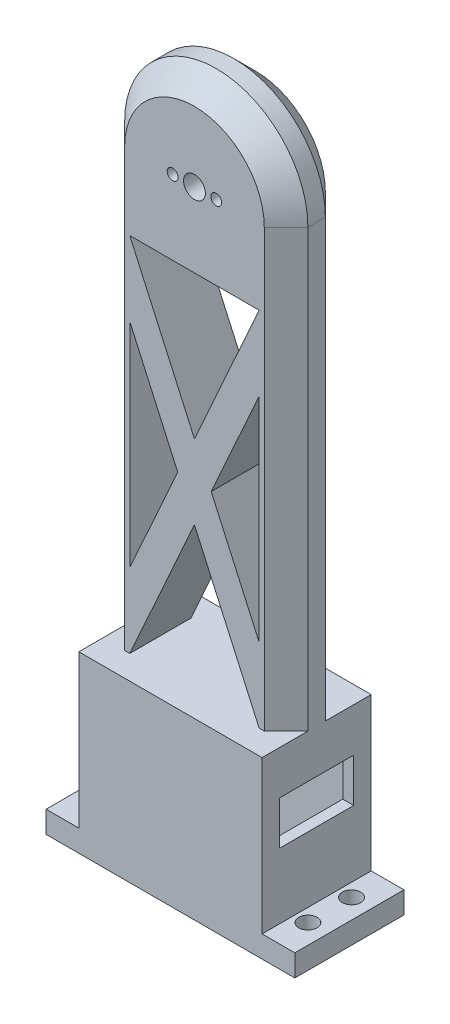
SolidWorks part; units mm, degrees
ref_plane "Front Plane" through (0, 0, 0) normal (0, 0, 1) x (1, 0, 0)
ref_plane "Top Plane" through (0, 0, 0) normal (0, 1, 0) x (1, 0, 0)
ref_plane "Right Plane" through (0, 0, 0) normal (1, 0, 0) x (0, 0, -1)
sketch "Sketch1" plane through (0, 0, 0) normal (0, 0, 1) x (1, 0, 0)
  line L2 (-21, 0) -> (-21, -100)
  line L3 (-21, -100) -> (21, -100)
  line L4 (21, 0) -> (21, -100)
  arc A1 (21, 0) -> (-21, 0) centre (0, 0) ccw
  point P1 (0, 0)
  dimension "D1" = 100
  dimension "D2" = 42
extrude "Boss-Extrude1" add sketch "Sketch1" along normal mid plane 14
sketch "Sketch2" plane through (0, -100, 0) normal (0, -1, 0) x (1, 0, 0)
  line L1 (21, -12.5) -> (-21, -12.5)
  line L2 (21, -12.5) -> (21, 12.5)
  line L3 (21, 12.5) -> (-21, 12.5)
  line L4 (-21, -12.5) -> (-21, 12.5)
  line L5 (21, -12.5) -> (-21, 12.5) construction
  line L6 (21, 12.5) -> (-21, -12.5) construction
  point P0 (0, 0)
  dimension "D1" = 42
  dimension "D2" = 25
extrude "Boss-Extrude2" add sketch "Sketch2" along normal blind 40 separate body
shell "Shell1" thickness 2.5 removed face at (0, -140, 0)
combine bodies "Combine1" operation type add bodies to combine 101 102
sketch "Sketch8" plane through (0, 0, 7) normal (0, 0, 1) x (1, 0, 0)
  line L0 (-10.25, 0) -> (10.25, 0)
  circle A0 centre (0, 0) radius 10.25
  circle A1 centre (-5, 0) radius 1.25
  circle A2 centre (5, 0) radius 1.25
  circle A3 centre (0, 0) radius 2.5
  dimension "D1" = 20.5
  dimension "D2" = 2.5
  dimension "D3" = 2.5
  dimension "D4" = 10
  dimension "D6" = 5
  dimension "D5" = 5.25
extrude "Cut-Extrude5" cut sketch "Sketch8" against normal up to next contours L0 A1 | L0 A1 | L0 A2 | L0 A2 | L0 A3 | L0 A3 | A3 region at (5, -0.5305, 7) region at (5, 0.5305, 7) region at (0, -1.061, 7) region at (0, 1.061, 7) region at (-5, 0.5305, 7) region at (-5, -0.5305, 7)
sketch "Sketch9" plane through (0, -140, 0) normal (0, -1, 0) x (1, 0, 0)
  line L5 (-21, -12.5) -> (21, -12.5) construction
  line L10 (-18.5, 12.5) -> (-28.5, 12.5)
  line L11 (-18.5, 12.5) -> (-18.5, -12.5)
  line L12 (-18.5, -12.5) -> (-28.5, -12.5)
  line L13 (-28.5, 12.5) -> (-28.5, -12.5)
  line L14 (21, 12.5) -> (-21, 12.5) construction
  line L15 (-18.5, 10) -> (-18.5, -10) construction
  line L16 (0, -12.5) -> (0, 12.5)
  line L17 (18.5, -12.5) -> (28.5, -12.5)
  line L18 (28.5, 12.5) -> (28.5, -12.5)
  line L19 (18.5, 12.5) -> (28.5, 12.5)
  line L20 (18.5, 12.5) -> (18.5, -12.5)
  point P18 (0, 0)
  dimension "D1" = 10
extrude "Boss-Extrude3" add sketch "Sketch9" against normal blind 5 contours L10 L13 L12 | L19 L17 L18 region at (-23.5, -140, 0) region at (23.5, -140, 0)
sketch "Sketch10" plane through (21, 0, 0) normal (1, 0, 0) x (0, 0, -1)
  line L0 (-12.5, -135) -> (-12.5, -100) construction
  line L1 (-8.5, -110) -> (8.5, -110)
  line L2 (-8.5, -110) -> (-8.5, -120)
  line L3 (-8.5, -120) -> (8.5, -120)
  line L4 (8.5, -110) -> (8.5, -120)
  line L5 (12.5, -135) -> (12.5, -100) construction
  line L6 (12.5, -100) -> (7, -100) construction
  dimension "D1" = 4
  dimension "D2" = 4
  dimension "D3" = 10
  dimension "D4" = 10
extrude "Cut-Extrude6" cut sketch "Sketch10" against normal up to next
sketch "Sketch12" plane through (0, 0, 7) normal (0, 0, 1) x (1, 0, 0)
  line L0 (21, 0) -> (21, -17.058)
  line L2 (14.8239, -34.116) -> (3.838, -58.529)
  line L3 (-21, -100) -> (-21, -117.058)
  line L4 (21, -100) -> (21, 0) construction
  line L5 (-21, -135) -> (-21, -100) construction
  line L6 (-21, -100) -> (21, -100) construction
  line L7 (-21, 0) -> (-21, -17.058)
  line L8 (-14.8239, -17.058) -> (0, -50)
  line L9 (-14.8239, -34.116) -> (-3.838, -58.529)
  line L10 (21, -100) -> (21, -117.058)
  line L11 (-21, 0) -> (-21, -100) construction
  line L12 (21, -135) -> (21, -100) construction
  line L13 (21, -100) -> (-21, -100) construction
  line L14 (0, -67.058) -> (14.8239, -100)
  line L15 (3.838, -58.529) -> (14.8239, -82.942)
  line L16 (-3.838, -58.529) -> (-14.8239, -82.942)
  line L17 (0, -67.058) -> (-14.8239, -100)
  line L18 (-14.8239, -17.058) -> (14.8239, -17.058)
  line L20 (-21, 0) -> (-21, -100)
  line L22 (-14.8239, -34.116) -> (-14.8239, -82.942)
  line L24 (21, 0) -> (21, -100)
  line L26 (14.8239, -34.116) -> (14.8239, -82.942)
  line L27 (-21, -17.058) -> (-21, -10.0998)
  line L28 (21, -17.058) -> (21, 0)
  line L30 (14.8239, -17.058) -> (0, -50)
  line L31 (-14.8239, -100) -> (14.8239, -100)
  line M28 (-21, -100) -> (21, -100)
  dimension "D2" = 7
extrude "Cut-Extrude8" cut sketch "Sketch12" against normal up to next contours L30 L18 L8 | L9 L22 L16 | L14 L17 M28 | L26 L2 L15 region at (11.162, -58.529, 7) region at (0, -28.0387, 7) region at (-11.162, -58.529, 7) region at (0, -89.0193, 7)
sketch "Sketch13" plane through (0, -140, 0) normal (0, -1, 0) x (1, 0, 0)
  line L0 (0, -10) -> (0, 10)
  line L1 (-18.5, -10) -> (18.5, -10) construction
  line L2 (18.5, 10) -> (-18.5, 10) construction
  circle A0 centre (24, 5) radius 2.1
  circle A1 centre (24, -5) radius 2.1
  arc A2 (-24, 2.9) -> (-24, 7.1) centre (-24, 5) ccw construction
  circle A3 centre (-24, 5) radius 2.1
  circle A4 centre (-24, -5) radius 2.1
  arc A5 (-24, 2.9) -> (-24, 7.1) centre (-24, 5) ccw
  arc A6 (-24, -7.1) -> (-24, -2.9) centre (-24, -5) ccw construction
  arc A7 (-24, -7.1) -> (-24, -2.9) centre (-24, -5) ccw
  point P16 (0, 0)
  point P19 (0, 0)
extrude "Cut-Extrude9" cut sketch "Sketch13" against normal up to next contours A3 | A4 | A0 | A1 region at (24, -140, 5) region at (24, -140, -5) region at (-24, -140, 5) region at (-24, -140, -5)
chamfer "Chamfer1" distance 5 angle 45 6 edges at (21, -50, 7) (-21, -50, 7) (0, 21, 7) (21, -50, -7) (-21, -50, -7) (0, 21, -7)
